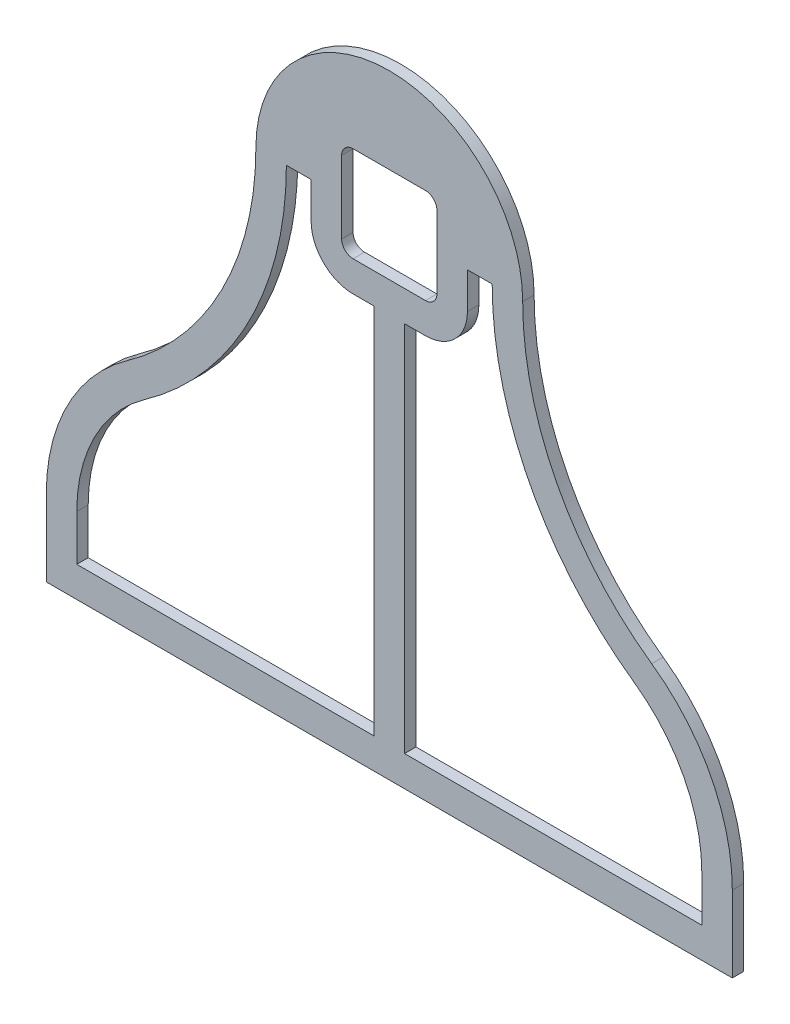
SolidWorks part; units mm, degrees
ref_plane "Plan de face" through (0, 0, 0) normal (0, 0, 1) x (1, 0, 0)
ref_plane "Plan de dessus" through (0, 0, 0) normal (0, 1, 0) x (1, 0, 0)
ref_plane "Plan de droite" through (0, 0, 0) normal (1, 0, 0) x (0, 0, -1)
sketch "Esquisse1" plane through (0, 0, 0) normal (0, 0, 1) x (1, 0, 0)
  line L1 (0, 0) -> (180, 0)
  line L2 (0, 0) -> (0, 300)
  line L3 (0, 300) -> (180, 300)
  line L4 (180, 0) -> (180, 300)
  dimension "D1" = 180
  dimension "D2" = 300
extrude "Boss.-Extru.1" add sketch "Esquisse1" along normal blind 15
sketch "Esquisse2" plane through (0, 0, 15) normal (0, 0, 1) x (1, 0, 0)
  line L0 (0, 300) -> (0, 0) construction
  line L1 (0, 8) -> (180, 8)
  line L2 (0, 8) -> (0, 16.1)
  line L3 (0, 16.1) -> (180, 16.1)
  line L4 (180, 8) -> (180, 16.1)
  line L5 (180, 0) -> (180, 300) construction
  line L6 (0, 0) -> (180, 0) construction
  dimension "D1" = 8.1
  dimension "D2" = 8
extrude "Enlèv. mat.-Extru.1" cut sketch "Esquisse2" against normal blind 5
sketch "Esquisse3" plane through (0, 0, 0) normal (-1, 0, 0) x (0, 0, 1)
  line L0 (0, 35) -> (0, 5)
  line L1 (0, 300) -> (0, 0) construction
  line L2 (0, 5) -> (15, 7.6449)
  line L3 (15, 300) -> (15, 16.1) construction
  line L4 (15, 7.6449) -> (15, 32.3551)
  line L5 (15, 20) -> (0, 20) construction
  line L6 (0, 35) -> (15, 32.3551)
  line L7 (15, 0) -> (0, 0) construction
  line L8 (0, 43) -> (15, 43) construction
  line L9 (15, 66) -> (0, 66) construction
  line L10 (0, 51) -> (15, 53.6449)
  line L11 (15, 78.3551) -> (15, 53.6449)
  line L12 (0, 81) -> (15, 78.3551)
  line L13 (0, 51) -> (0, 81)
  dimension "D1" = 30
  dimension "D2" = 10
  dimension "D3" = 20
  dimension "D4" = 46
extrude "Enlèv. mat.-Extru.2" cut sketch "Esquisse3" against normal blind 10
extrude "Enlèv. mat.-Extru.3" cut sketch "Esquisse3<2>" along normal blind 10 from surface starting at face at (180, 81.025, 10)
sketch "Esquisse3<2>" plane through (0, 0, 0) normal (-1, 0, 0) x (0, 0, 1) same geometry as "Esquisse3"
sketch "Esquisse4" plane through (0, 0, 0) normal (0, 0, -1) x (-1, 0, 0)
  line L0 (-90, 0) -> (-90, 300) construction
  line L1 (0, 0) -> (-180, 0) construction
  line L2 (-180, 300) -> (0, 300) construction
  line L4 (0, 300) -> (0, 81) construction
  line L5 (-55, 265) -> (-55, 300) construction
  line L6 (0, 189.0066) -> (0, 300)
  line L7 (0, 300) -> (-90, 310)
  line L8 (-90, 300) -> (-90, 310) construction
  line L9 (-125, 265) -> (-125, 300) construction
  line L10 (-180, 300) -> (-90, 310)
  line L11 (-180, 189.0066) -> (-180, 300)
  line L12 (-180, 81) -> (-180, 300) construction
  arc A0 (-125, 265) -> (-55, 265) centre (-90, 265) cw
  arc A1 (-55, 265) -> (0, 189.0066) centre (25, 265) ccw
  arc A2 (-125, 265) -> (-180, 189.0066) centre (-205, 265) cw
  dimension "D1" = 35
  dimension "D2" = 80
  dimension "D3" = 10
extrude "Enlèv. mat.-Extru.4" cut sketch "Esquisse4" against normal through all both and the other way through all
fillet "Congé1" radius 50 2 edges
sketch "Esquisse5" plane through (0, 0, 0) normal (0, 0, -1) x (-1, 0, 0)
  line L0 (-90, 0) -> (-90, 265) construction
  line L1 (0, 0) -> (-180, 0) construction
  line L3 (-102.5, 277.5) -> (-77.5, 277.5)
  line L4 (-102.5, 277.5) -> (-102.5, 252.5)
  line L5 (-102.5, 252.5) -> (-77.5, 252.5)
  line L6 (-77.5, 277.5) -> (-77.5, 252.5)
  line L7 (-102.5, 277.5) -> (-77.5, 252.5) construction
  line L8 (-102.5, 252.5) -> (-77.5, 277.5) construction
  arc A0 (-55, 265) -> (-125, 265) centre (-90, 265) ccw construction
  point P11 (-90, 300)
  dimension "D1" = 25
  dimension "D2" = 25
  dimension "D3" = 35
extrude "Enlèv. mat.-Extru.5" cut sketch "Esquisse5" against normal through all both and the other way through all
fillet "Congé2" radius 3 4 edges at (77.5, 277.5, 7.5) (102.5, 277.5, 7.5) (77.5, 252.5, 7.5) (102.5, 252.5, 7.5)
chamfer "Chanfrein1" [suppressed] distance 2 angle 45
sketch "Esquisse6" plane through (0, 0, 15) normal (0, 0, 1) x (1, 0, 0)
  line L0 (180, 78.3551) -> (180, 158.8162) construction
  line L1 (0, 0) -> (180, 0)
  line L2 (0, 0) -> (0, 138.8162)
  line L3 (0, 138.8162) -> (180, 138.8162)
  line L4 (180, 0) -> (180, 138.8162)
  arc A0 (21.1538, 199.6561) -> (0, 158.8162) centre (50, 158.8162) ccw construction
  dimension "D1" = 20
extrude "Enlèv. mat.-Extru.6" cut sketch "Esquisse6" against normal through all both and the other way through all
sketch "Esquisse8" plane through (0, 0, 15) normal (0, 0, 1) x (1, 0, 0)
  line L0 (102.5, 274.5) -> (102.5, 255.5) construction
  line L1 (80.5, 277.5) -> (99.5, 277.5) construction
  line L2 (77.5, 255.5) -> (77.5, 274.5) construction
  line L3 (0, 158.8162) -> (0, 138.8162)
  line L4 (0, 138.8162) -> (180, 138.8162)
  line L5 (180, 138.8162) -> (180, 158.8162)
  line L6 (0, 158.8162) -> (0, 138.8162)
  line L7 (0, 138.8162) -> (180, 138.8162)
  line L8 (180, 138.8162) -> (180, 158.8162)
  line L9 (99.5, 252.5) -> (80.5, 252.5) construction
  line L10 (102.5, 274.5) -> (102.5, 255.5)
  line L11 (80.5, 277.5) -> (99.5, 277.5)
  line L12 (77.5, 255.5) -> (77.5, 274.5)
  line L13 (99.5, 252.5) -> (80.5, 252.5)
  arc A0 (99.5, 252.5) -> (102.5, 255.5) centre (99.5, 255.5) ccw construction
  arc A1 (102.5, 274.5) -> (99.5, 277.5) centre (99.5, 274.5) ccw construction
  arc A2 (80.5, 277.5) -> (77.5, 274.5) centre (80.5, 274.5) ccw construction
  arc A3 (77.5, 255.5) -> (80.5, 252.5) centre (80.5, 255.5) ccw construction
  arc A4 (99.5, 252.5) -> (102.5, 255.5) centre (99.5, 255.5) ccw
  arc A5 (180, 158.8162) -> (158.8462, 199.6561) centre (130, 158.8162) ccw
  arc A6 (125, 265) -> (158.8462, 199.6561) centre (205, 265) ccw
  arc A7 (125, 265) -> (55, 265) centre (90, 265) ccw
  arc A8 (21.1538, 199.6561) -> (55, 265) centre (-25, 265) ccw
  arc A9 (21.1538, 199.6561) -> (0, 158.8162) centre (50, 158.8162) ccw
  arc A10 (180, 158.8162) -> (158.8462, 199.6561) centre (130, 158.8162) ccw
  arc A11 (125, 265) -> (158.8462, 199.6561) centre (205, 265) ccw
  arc A12 (125, 265) -> (55, 265) centre (90, 265) ccw
  arc A13 (21.1538, 199.6561) -> (55, 265) centre (-25, 265) ccw
  arc A14 (21.1538, 199.6561) -> (0, 158.8162) centre (50, 158.8162) ccw
  arc A15 (102.5, 274.5) -> (99.5, 277.5) centre (99.5, 274.5) ccw
  arc A16 (80.5, 277.5) -> (77.5, 274.5) centre (80.5, 274.5) ccw
  arc A17 (77.5, 255.5) -> (80.5, 252.5) centre (80.5, 255.5) ccw
  dimension "D1" = 0
extrude "Enlèv. mat.-Extru.7" cut sketch "Esquisse8" against normal blind 12
sketch "Esquisse9" plane through (0, 0, 3) normal (0, 0, 1) x (1, 0, 0)
  line L1 (110.5, 255.5) -> (110.5, 265)
  line L2 (80.5, 244.5) -> (99.5, 244.5)
  line L5 (80.5, 244.5) -> (99.5, 244.5)
  line L6 (8, 158.8162) -> (8, 146.8162)
  line L7 (8, 146.8162) -> (172, 146.8162)
  line L8 (172, 146.8162) -> (172, 158.8162)
  line L9 (8, 158.8162) -> (8, 146.8162)
  line L10 (8, 146.8162) -> (172, 146.8162)
  line L11 (172, 146.8162) -> (172, 158.8162)
  line L12 (110.5, 265) -> (117, 265)
  line L13 (69.5, 255.5) -> (69.5, 265)
  line L14 (69.5, 265) -> (63, 265)
  arc A4 (99.5, 244.5) -> (110.5, 255.5) centre (99.5, 255.5) ccw
  arc A6 (69.5, 255.5) -> (80.5, 244.5) centre (80.5, 255.5) ccw
  arc A7 (99.5, 244.5) -> (110.5, 255.5) centre (99.5, 255.5) ccw
  arc A8 (69.5, 255.5) -> (80.5, 244.5) centre (80.5, 255.5) ccw
  arc A10 (25.7692, 193.1217) -> (8, 158.8162) centre (50, 158.8162) ccw
  arc A11 (172, 158.8162) -> (154.2308, 193.1217) centre (130, 158.8162) ccw
  arc A12 (117, 265) -> (154.2308, 193.1217) centre (205, 265) ccw
  arc A13 (117, 265) -> (63, 265) centre (90, 265) ccw
  arc A14 (25.7692, 193.1217) -> (63, 265) centre (-25, 265) ccw
  arc A15 (25.7692, 193.1217) -> (8, 158.8162) centre (50, 158.8162) ccw
  arc A16 (172, 158.8162) -> (154.2308, 193.1217) centre (130, 158.8162) ccw
  arc A17 (117, 265) -> (154.2308, 193.1217) centre (205, 265) ccw
  arc A19 (25.7692, 193.1217) -> (63, 265) centre (-25, 265) ccw
  point P0 (0, 0)
  dimension "D1" = 8
  dimension "D2" = 8
extrude "Enlèv. mat.-Extru.8" cut sketch "Esquisse9" against normal through all both and the other way through all
sketch "Esquisse10" plane through (0, 0, 3) normal (0, 0, 1) x (1, 0, 0)
  line L0 (90, 146.8162) -> (90, 244.5) construction
  line L1 (8, 146.8162) -> (172, 146.8162) construction
  line L2 (99.5, 244.5) -> (80.5, 244.5) construction
  line L3 (94, 146.8162) -> (86, 146.8162)
  line L4 (86, 146.8162) -> (86, 244.5)
  line L5 (86, 244.5) -> (94, 244.5)
  line L6 (94, 146.8162) -> (94, 244.5)
  dimension "D1" = 8
extrude "Boss.-Extru.2" add sketch "Esquisse10" against normal up to vertex (3 mm away) up to point (8, 146.8162, 0)
